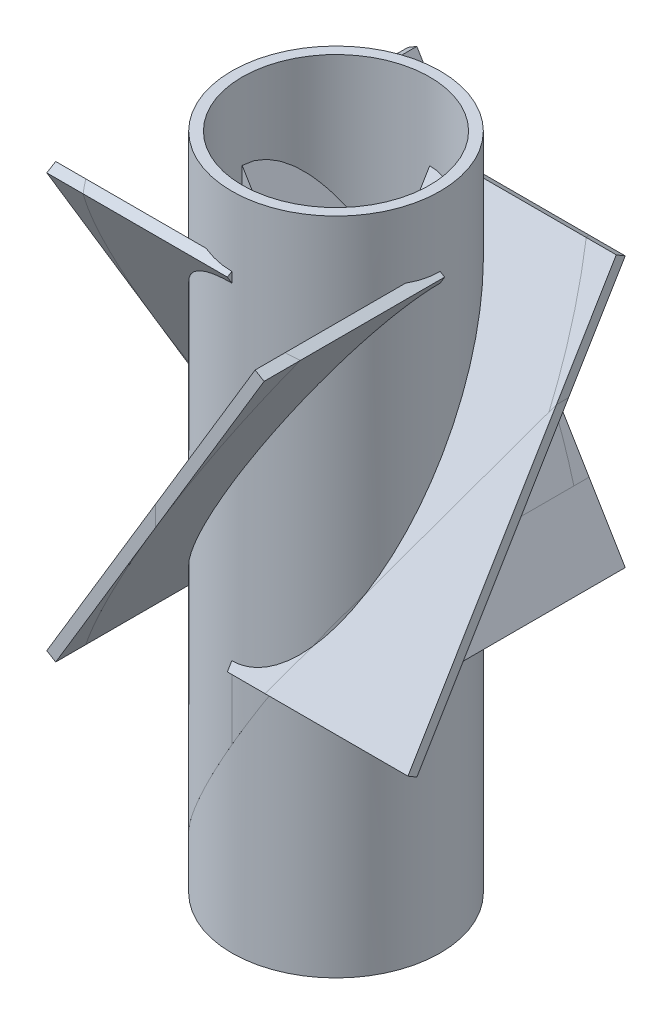
SolidWorks part; units mm, degrees
ref_plane "前视基准面" through (0, 0, 0) normal (0, 0, 1) x (1, 0, 0)
ref_plane "上视基准面" through (0, 0, 0) normal (0, 1, 0) x (1, 0, 0)
ref_plane "右视基准面" through (0, 0, 0) normal (1, 0, 0) x (0, 0, -1)
sketch "草图1" plane through (0, 0, 0) normal (0, 1, 0) x (1, 0, 0)
  circle A0 centre (0, 0) radius 30
  circle A1 centre (0, 0) radius 27
  dimension "D1" = 60
  dimension "D2" = 54
extrude "凸台-拉伸3" add sketch "草图1" along normal blind 190
ref_axis "基准轴1" through (0, 190, 0) along (0, -1, 0)
sketch "草图3" plane through (0, 0, 0) normal (0, 0, 1) x (1, 0, 0)
  line L0 (-30, 190) -> (-30, 170) construction
  line L1 (-30, 190) -> (-30, 0) construction
  line L2 (-30, 170) -> (-30, 70) construction
  line L3 (-30, 170) -> (30, 170) construction
  line L4 (30, 0) -> (30, 190) construction
  line L5 (-30, 70) -> (30, 70) construction
  line L6 (-30, 120) -> (0, 120) construction
  line L7 (0, 190) -> (0, 0) construction
  dimension "D1" = 20
  dimension "D2" = 100
sketch "草图4" plane through (0, 0, 0) normal (1, 0, 0) x (0, 0, -1)
  line L0 (-30, 190) -> (-30, 170) construction
  line L1 (-30, 170) -> (-30, 70) construction
  line L2 (-30, 190) -> (-30, 0) construction
  line L3 (-30, 170) -> (30, 170) construction
  line L4 (30, 0) -> (30, 190) construction
  line L5 (-30, 70) -> (30, 70) construction
  line L6 (-30, 120) -> (0, 120) construction
  dimension "D1" = 20
  dimension "D2" = 100
ref_axis "叶片轴1" through (0, 170, 30) along (0, -0.8575, -0.5145)
ref_axis "叶片轴2" through (0, 170, -30) along (0, -0.8575, 0.5145)
ref_axis "叶片轴3" through (-30, 170, 0) along (0.5145, -0.8575, 0)
ref_axis "叶片轴4" through (30, 170, 0) along (-0.5145, -0.8575, 0)
ref_plane "基准面6" through (0, 31.7647, -52.9412) normal (0, -0.5145, 0.8575) x (0, -0.8575, -0.5145)
ref_plane "基准面7" through (0, 31.7647, 52.9412) normal (0, 0.5145, 0.8575) x (0, -0.8575, 0.5145)
ref_plane "基准面8" through (52.9412, 31.7647, 0) normal (-0.8575, -0.5145, 0) x (0.5145, -0.8575, 0)
ref_plane "基准面9" through (-52.9412, 31.7647, 0) normal (-0.8575, 0.5145, 0) x (-0.5145, -0.8575, 0)
sketch "草图5" plane through (0, 31.7647, -52.9412) normal (0, -0.5145, 0.8575) x (0, -0.8575, -0.5145)
  line L6 (-75.4594, 0) -> (-44.5896, 0) construction
  line L8 (-44.5896, 0) -> (-161.2087, 0)
  line L9 (-44.5896, 0) -> (-44.5896, -52)
  line L10 (-44.5896, -52) -> (-161.2087, -52)
  line L11 (-161.2087, 0) -> (-161.2087, -52)
  dimension "D1" = 52
extrude "凸台-拉伸4" add sketch "草图5" along normal mid plane 3
sketch "草图6" plane through (0, 31.7647, 52.9412) normal (0, 0.5145, 0.8575) x (0, -0.8575, 0.5145)
  line L0 (-130.3389, 0) -> (-161.2087, 0) construction
  line L1 (-161.2087, 0) -> (-44.5896, 0)
  line L2 (-161.2087, 0) -> (-161.2087, 52)
  line L3 (-161.2087, 52) -> (-44.5896, 52)
  line L4 (-44.5896, 0) -> (-44.5896, 52)
  dimension "D1" = 52
extrude "凸台-拉伸5" add sketch "草图6" along normal mid plane 3
sketch "草图7" plane through (52.9412, 31.7647, 0) normal (-0.8575, -0.5145, 0) x (0.5145, -0.8575, 0)
  line L0 (-161.2087, 0) -> (-130.3389, 0) construction
  line L1 (-161.2087, 0) -> (-44.5896, 0)
  line L2 (-161.2087, 0) -> (-161.2087, -52)
  line L3 (-161.2087, -52) -> (-44.5896, -52)
  line L4 (-44.5896, 0) -> (-44.5896, -52)
  line L5 (-178.3585, 0) -> (-161.2087, 0) construction
  dimension "D1" = 52
extrude "凸台-拉伸6" add sketch "草图7" along normal mid plane 3
sketch "草图8" plane through (-52.9412, 31.7647, 0) normal (-0.8575, 0.5145, 0) x (-0.5145, -0.8575, 0)
  line L0 (-130.3389, 0) -> (-161.2087, 0) construction
  line L1 (-161.2087, 0) -> (-44.5896, 0)
  line L2 (-161.2087, 0) -> (-161.2087, 52)
  line L3 (-161.2087, 52) -> (-44.5896, 52)
  line L4 (-44.5896, 0) -> (-44.5896, 52)
extrude "凸台-拉伸7" add sketch "草图8" along normal mid plane 3
sketch "草图10" plane through (0, 0, 0) normal (0, 0, 1) x (1, 0, 0)
  line L0 (-30, 0) -> (64.2181, 163.1905)
  line L1 (-30, 70) -> (-30, 0) construction
  dimension "D1" = 30
split "分割1" trim tools "草图10" bodies to split 112 resulting bodies 114 115
sketch "草图11" plane through (0, 0, 0) normal (0, 1, 0) x (1, 0, 0)
  line L0 (-30, 0) -> (30, 0) construction
  circle A0 centre (0, 0) radius 27
split "分割2" trim tools "草图11" bodies to split 114 resulting bodies 116 117
sketch "草图12" plane through (0, 0, 0) normal (0, 1, 0) x (1, 0, 0)
  circle A0 centre (0, 0) radius 52
  dimension "D1" = 104
split "分割3" trim tools "草图12" bodies to split 116 resulting bodies 118 119 120 121 122 123 124 125
